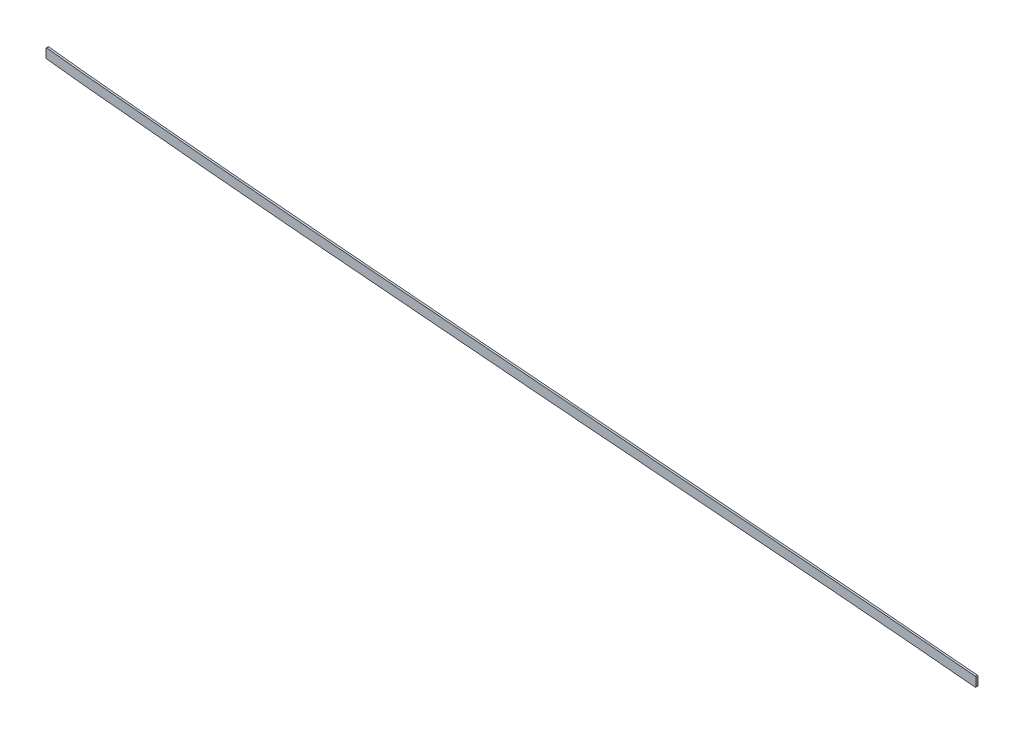
SolidWorks part; units mm, degrees
ref_plane "Front Plane" through (0, 0, 0) normal (0, 0, 1) x (1, 0, 0)
ref_plane "Top Plane" through (0, 0, 0) normal (0, 1, 0) x (1, 0, 0)
ref_plane "Right Plane" through (0, 0, 0) normal (1, 0, 0) x (0, 0, -1)
sketch "Sketch2" plane through (0, 0, 0) normal (0, 0, 1) x (1, 0, 0)
  line L0 (0, 0) -> (266.9553, 0) construction
  line L1 (825.5, 263.7287) -> (825.5, 174.6622)
  line L2 (2311.4, 135.8299) -> (2311.4, 52.664)
  spline S0 degree 5 poles (818.067, 264.7065) (827.0431, 263.4992) (836.0291, 262.3734) (845.0868, 261.3058) (891.3865, 256.087) (937.6862, 251.7792) (973.4521, 248.2277) (1071.9467, 239.0511) (1170.4413, 229.7315) (1231.7919, 224.5039) (1324.8993, 216.7906) (1418.0067, 209.0401) (1449.7429, 206.3618) (1636.9286, 190.5211) (1824.1143, 175.4092) (1979.9669, 164.2997) (2156.2686, 150.4144) (2332.5703, 133.8572) (2354.213, 131.7851) (2436.3555, 123.724) (2518.4981, 114.8591) (2579.4813, 107.7425) (2639.6368, 100.3834) (2699.7923, 92.6045) knots 77.930822 77.930822 77.930822 77.930822 77.930822 77.930822 82.465793 82.465793 82.465793 100.79329 100.79329 100.79329 131.098954 131.098954 131.098954 146.769198 146.769198 146.769198 223.533959 223.533959 223.533959 233.943117 233.943117 233.943117 264.216209 264.216209 264.216209 264.216209 264.216209 264.216209 weights 1 1 1 1 1 1 1 1 1 1 1 1 1 1 1 1 1 1 1 1 1 1 1 1
  spline S1 degree 1 poles (816.0355, 249.6025) (2697.8379, 77.4903) knots 0 0 1 1 construction
  spline S2 degree 3 poles (816.0355, 249.6025) (820.896, 248.9488) (830.6112, 247.6997) (845.2811, 245.9534) (860.0865, 244.2956) (879.8307, 242.1866) (904.37, 239.6983) (933.571, 236.8322) (962.6427, 234.0237) (991.7626, 231.242) (1021.072, 228.4759) (1060.3764, 224.797) (1109.513, 220.1844) (1168.5112, 214.8171) (1227.5001, 209.6621) (1306.1332, 203.0212) (1404.3615, 194.9207) (1522.2399, 184.9181) (1640.1829, 175.167) (1758.1654, 165.7576) (1876.1554, 156.5909) (1994.0875, 147.4533) (2092.2687, 139.6242) (2170.748, 133.0797) (2219.7717, 128.8422) (2258.984, 125.3472) (2288.3795, 122.6709) (2317.8122, 119.9317) (2347.5515, 117.1004) (2377.1599, 114.2101) (2406.4697, 111.269) (2435.8183, 108.2401) (2474.9139, 104.0902) (2523.7162, 98.6933) (2582.0419, 91.9123) (2640.0752, 84.8576) (2678.5742, 79.9814) (2697.8379, 77.4903) knots 77.930822 77.930822 77.930822 77.930822 79.386176 80.841531 82.296885 83.75224 86.662949 89.573658 92.484367 95.395077 98.305786 101.216495 107.037913 112.859332 118.68075 124.502168 136.145005 147.787842 159.430678 171.073515 182.716352 194.359189 206.002025 211.823444 217.644862 220.555571 223.46628 226.37699 229.287699 232.198408 235.109117 238.019826 240.930535 246.751954 252.573372 258.39479 264.216209 264.216209 264.216209 264.216209
  spline S3 degree 5 poles (818.067, -264.7065) (827.0431, -263.4992) (836.0291, -262.3734) (845.0868, -261.3058) (891.3865, -256.087) (937.6862, -251.7792) (973.4521, -248.2277) (1071.9467, -239.0511) (1170.4413, -229.7315) (1231.7919, -224.5039) (1324.8993, -216.7906) (1418.0067, -209.0401) (1449.7429, -206.3618) (1636.9286, -190.5211) (1824.1143, -175.4092) (1979.9669, -164.2997) (2156.2686, -150.4144) (2332.5703, -133.8572) (2354.213, -131.7851) (2436.3555, -123.724) (2518.4981, -114.8591) (2579.4813, -107.7425) (2639.6368, -100.3834) (2699.7923, -92.6045) knots 77.930822 77.930822 77.930822 77.930822 77.930822 77.930822 82.465793 82.465793 82.465793 100.79329 100.79329 100.79329 131.098954 131.098954 131.098954 146.769198 146.769198 146.769198 223.533959 223.533959 223.533959 233.943117 233.943117 233.943117 264.216209 264.216209 264.216209 264.216209 264.216209 264.216209 weights 1 1 1 1 1 1 1 1 1 1 1 1 1 1 1 1 1 1 1 1 1 1 1 1
  point P2 (0, 0)
  dimension "D1" = 818.067
  dimension "D2" = 825.5
  dimension "D3" = 2311.4
  dimension "D4" = 15.24
extrude "Boss-Extrude1" add sketch "Sketch2" along normal mid plane 3.175 contours L1 S2 L2 S0 region at (1568.2463, 189.9349, 0)
fillet "Fillet1" radius 1.27 4 edges at (2311.4, 120.5233, 0) (825.5, 248.3644, 0)
